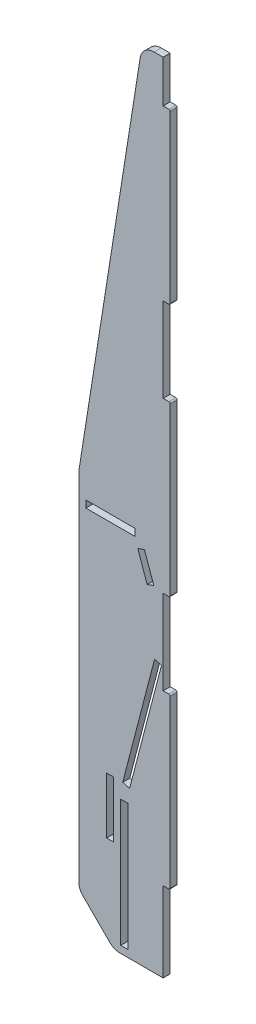
SolidWorks part; units mm, degrees
ref_plane "Front" through (0, 0, 0) normal (0, 0, 1) x (1, 0, 0)
ref_plane "Top" through (0, 0, 0) normal (0, 1, 0) x (1, 0, 0)
ref_plane "Right" through (0, 0, 0) normal (1, 0, 0) x (0, 0, -1)
sketch "Sketch1" plane through (0, 0, 0) normal (0, 0, 1) x (1, 0, 0)
  line L0 (80, 33.22) -> (20, 33.22)
  line L3 (20, 600) -> (80, 600)
  line L4 (80, 33.22) -> (80, 90)
  line L5 (20, 600) -> (20, 33.22)
  line L6 (80, 570) -> (80, 600)
  line L7 (80, 90) -> (85, 90)
  line L9 (80, 210) -> (85, 210)
  line L10 (85, 90) -> (85, 210)
  line L11 (80, 270) -> (85, 270)
  line L13 (80, 390) -> (85, 390)
  line L14 (85, 270) -> (85, 390)
  line L15 (80, 570) -> (85, 570)
  line L17 (80, 450) -> (85, 450)
  line L18 (85, 570) -> (85, 450)
  line L19 (80, 390) -> (80, 450)
  line L20 (80, 210) -> (80, 270)
  dimension "D1" = 600
  dimension "D2" = 120
  dimension "D3" = 33.22
  dimension "D4" = 20
  dimension "D5" = 60
  dimension "D6" = 120
  dimension "D7" = 120
  dimension "D8" = 5
  dimension "D9" = 5
  dimension "D10" = 5
  dimension "D11" = 30
  dimension "D12" = 60
  dimension "D13" = 60
extrude "Boss-Extrude1" add sketch "Sketch1" along normal blind 5
sketch "Sketch2" plane through (0, 0, 5) normal (0, 0, 1) x (1, 0, 0)
  line L0 (80, 600) -> (20, 600) construction
  line L1 (25, 300) -> (65, 300) construction
  line L2 (25, 300) -> (25, 295) construction
  line L3 (25, 295) -> (65, 295) construction
  line L4 (65, 300) -> (65, 295) construction
  line L5 (80, 33.22) -> (80, 90) construction
  line L6 (65, 295) -> (75, 266.7157) construction
  line L7 (75, 266.7157) -> (70.286, 265.0491) construction
  line L8 (70.286, 265.0491) -> (60.286, 293.3333) construction
  line L9 (60.286, 293.3333) -> (65, 295) construction
  line L10 (66.6667, 290.286) -> (61.9526, 288.6193)
  line L11 (61.9526, 288.6193) -> (68.6193, 269.7631)
  line L12 (68.6193, 269.7631) -> (73.3333, 271.4298)
  line L13 (73.3333, 271.4298) -> (66.6667, 290.286)
  line L14 (80, 230) -> (75.1609, 231.258) construction
  line L15 (75.1609, 231.258) -> (50, 134.4751) construction
  line L16 (50, 134.4751) -> (54.8391, 133.2171) construction
  line L17 (54.8391, 133.2171) -> (80, 230) construction
  line L18 (73.9028, 226.4189) -> (51.258, 139.3143)
  line L19 (73.9028, 226.4189) -> (78.7915, 225.148)
  line L20 (51.258, 139.3143) -> (56.1468, 138.0433)
  line L21 (78.7915, 225.148) -> (56.1468, 138.0433)
  line L23 (54.8391, 133.2171) -> (49.8391, 133.2171) construction
  line L24 (54.8391, 133.2171) -> (54.8391, 33.2171) construction
  line L25 (54.8391, 33.2171) -> (49.8391, 33.2171) construction
  line L26 (49.8391, 133.2171) -> (49.8391, 33.2171) construction
  line L27 (49.8391, 128.2171) -> (54.8391, 128.2171)
  line L28 (49.8391, 128.2171) -> (49.8391, 38.2171)
  line L29 (49.8391, 38.2171) -> (54.8391, 38.2171)
  line L30 (54.8391, 128.2171) -> (54.8391, 38.2171)
  line L31 (39.8391, 139.3143) -> (44.8391, 139.3143)
  line L32 (39.8391, 139.3143) -> (39.8391, 99.3143)
  line L33 (39.8391, 99.3143) -> (44.8391, 99.3143)
  line L34 (44.8391, 139.3143) -> (44.8391, 99.3143)
  line L35 (60, 300) -> (25, 300)
  line L36 (60, 300) -> (60, 295)
  line L37 (60, 295) -> (25, 295)
  line L38 (25, 300) -> (25, 295)
  point P30 (52.3391, 33.2171)
  dimension "D1" = 300
  dimension "D2" = 5
  dimension "D3" = 5
  dimension "D4" = 15
  dimension "D5" = 5
  dimension "D6" = 20
  dimension "D7" = 5
  dimension "D8" = 30
  dimension "D9" = 5
  dimension "D10" = 5
  dimension "D11" = 370
  dimension "D12" = 30
  dimension "D13" = 100
  dimension "D14" = 5
  dimension "D15" = 5
  dimension "D16" = 5
  dimension "D17" = 100
  dimension "D18" = 5
  dimension "D19" = 5
  dimension "D20" = 5
  dimension "D21" = 5
  dimension "D22" = 40
  dimension "D23" = 35
extrude "Cut-Extrude1" cut sketch "Sketch2" against normal blind 10
sketch "Sketch3" plane through (0, 0, 5) normal (0, 0, 1) x (1, 0, 0)
  line L0 (20, 315) -> (65, 600)
  line L1 (20, 600) -> (20, 33.22) construction
  line L2 (80, 600) -> (20, 600) construction
  line L4 (20, 315) -> (1.5136, 616.0876)
  line L5 (1.5136, 616.0876) -> (65, 600)
  line L6 (45, 33.22) -> (20, 58.22)
  line L7 (20, 33.22) -> (80, 33.22) construction
  line L8 (20, 58.22) -> (13.4525, 20.5561)
  line L9 (13.4525, 20.5561) -> (45, 33.22)
  line L10 (60, 300) -> (25, 300) construction
  dimension "D1" = 15
  dimension "D2" = 15
  dimension "D3" = 25
  dimension "D4" = 25
extrude "Cut-Extrude2" cut sketch "Sketch3" against normal blind 10
fillet "Fillet1" radius 1 6 edges at (85, 570, 2.5) (85, 450, 2.5) (85, 390, 2.5) (85, 270, 2.5) (85, 210, 2.5) (85, 90, 2.5)
fillet "Fillet2" radius 10 4 edges at (65, 600, 2.5) (20, 315, 2.5) (20, 58.22, 2.5) (45, 33.22, 2.5)
